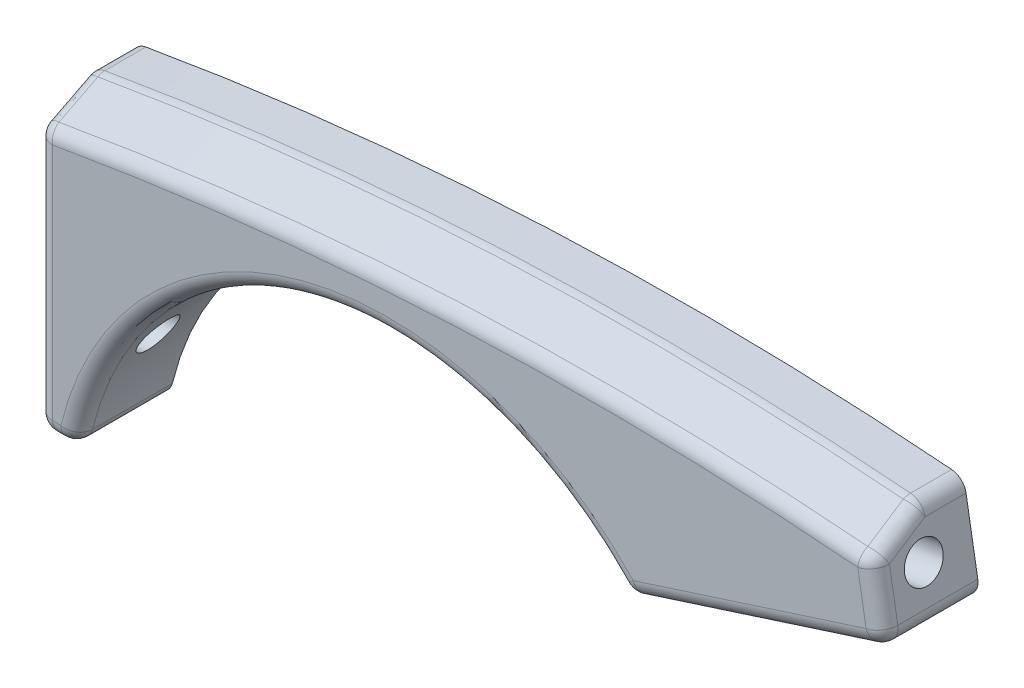
SolidWorks part; units mm, degrees
ref_plane "Front Plane" through (0, 0, 0) normal (0, 0, 1) x (1, 0, 0)
ref_plane "Top Plane" through (0, 0, 0) normal (0, 1, 0) x (1, 0, 0)
ref_plane "Right Plane" through (0, 0, 0) normal (1, 0, 0) x (0, 0, -1)
sketch "Sketch1" plane through (0, 0, 0) normal (0, 0, 1) x (1, 0, 0)
  line L0 (0, 0) -> (0, -28.575)
  line L2 (82.55, 3.81) -> (84.1536, -5.579)
  line L3 (0, -28.575) -> (3.6869, -28.575)
  line L4 (244.467, -237.1135) -> (141.8498, -254.6403) construction
  line L5 (84.1536, -5.579) -> (58.7536, -13.751)
  arc A1 (0, 0) -> (82.55, 3.81) centre (55.7888, -312.5602) cw
  circle A2 centre (34.925, -34.925) radius 31.877 construction
  arc A3 (3.6869, -28.575) -> (58.7536, -13.751) centre (34.925, -34.925) cw
  dimension "D1" = 31.877
  dimension "D2" = 317.5
  dimension "D3" = 82.55
  dimension "D4" = 28.575
  dimension "D5" = 9.525
  dimension "D6" = 25.4
  dimension "D7" = 3.81
extrude "Boss-Extrude1" add sketch "Sketch1" along normal blind 9.525
chamfer "Chamfer1" distance 5.08 distance2 2.54 1 edges at (41.1505, 4.6022, 9.525) first distance on face at (41.2128, 3.2536, 4.7625)
sketch "Sketch2" plane through (80.8424, 13.8077, 0) normal (0.9857, 0.1684, 0) x (0, 0, -1)
  circle A0 centre (-4.7625, -14.7218) radius 1.905
  arc A1 (-6.8625, -14.7218) -> (-2.6625, -14.7218) centre (-4.7625, -14.7218) ccw construction
  dimension "D1" = 3.81
extrude "Cut-Extrude1" cut sketch "Sketch2" against normal blind 12.7
sketch "Sketch3" plane through (0, 0, 0) normal (-1, 0, 0) x (0, 0, 1)
  line L0 (4.7625, -9.525) -> (4.7625, 0.6235) construction
  line L2 (-25.4707, 8.5908) -> (-40.0974, 14.7494) construction
  line L3 (4.7625, -19.05) -> (4.7625, -29.1985) construction
  circle A0 centre (4.7625, -9.525) radius 1.905
  circle A1 centre (4.7625, -19.05) radius 1.905
  arc A2 (5.846, -11.3038) -> (3.679, -7.7462) centre (4.7625, -9.525) ccw construction
  arc A3 (5.846, -20.8288) -> (3.679, -17.2712) centre (4.7625, -19.05) ccw construction
  dimension "D3" = 3.81
extrude "Cut-Extrude2" cut sketch "Sketch3" against normal up to next
fillet "Fillet1" radius 1.5875 15 edges at (71.4536, -9.665, 9.525) (26.6387, -4.1438, 9.525) (1.8434, -28.575, 9.525) (0, -15.5777, 9.525) (83.5727, -2.1781, 9.525) (41.37, 2.0696, 9.525) (41.1505, 4.6022, 4.445) (58.7536, -13.751, 4.7625) (3.6869, -28.575, 4.7625) (0, 0, 2.2225) (0, -28.575, 4.7625) (84.1536, -5.579, 4.7625) (82.55, 3.81, 2.2225)
